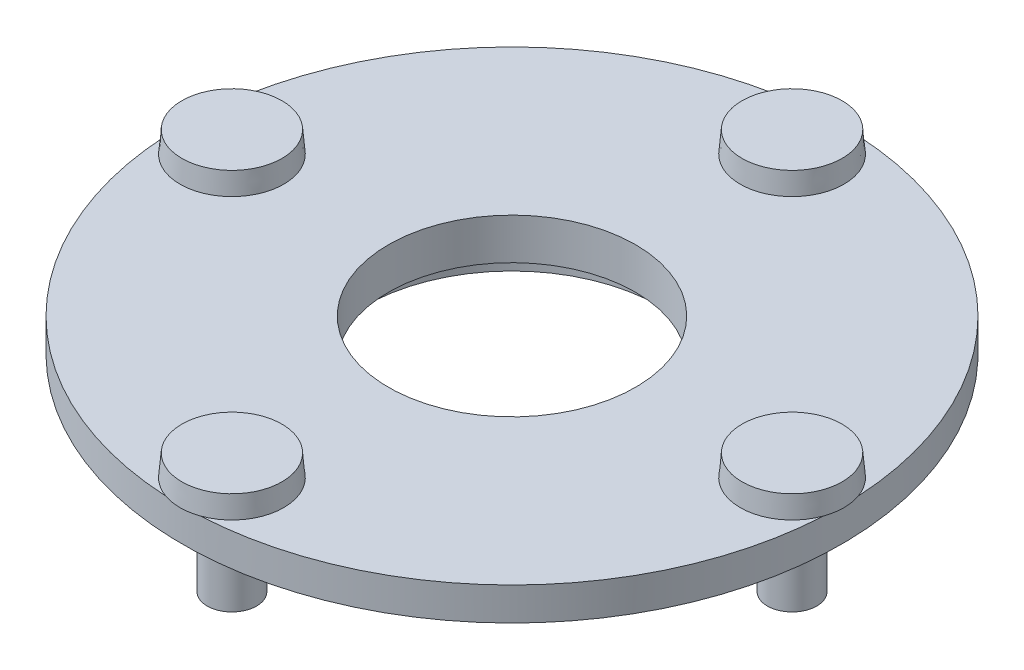
SolidWorks part; units mm, degrees
material "6061"
ref_plane "Front" through (0, 0, 0) normal (0, 0, 1) x (1, 0, 0)
ref_plane "Top" through (0, 0, 0) normal (0, 1, 0) x (1, 0, 0)
ref_plane "Right" through (0, 0, 0) normal (1, 0, 0) x (0, 0, -1)
sketch "Sketch1" plane through (0, 0, 0) normal (0, 0, 1) x (1, 0, 0)
  line L0 (0, -5.1764) -> (0, 49.1125) construction
  line L2 (7.5, 0) -> (20, 0)
  line L3 (7.5, 0) -> (7.5, 4)
  line L4 (7.5, 4) -> (20, 4)
  line L5 (20, 0) -> (20, 4)
  dimension "D1" = 40
  dimension "D2" = 15
  dimension "D3" = 4
revolve "Revolve1" add sketch "Sketch1" angle 360 about L0
sketch "Sketch2" plane through (0, 0, 0) normal (0, 0, 1) x (1, 0, 0)
  line L0 (0, -1.2334) -> (0, 5.5547) construction
  line L1 (-20, 0) -> (20, 0) construction
  line L2 (20, 0) -> (14, 0)
  line L3 (20, 0) -> (20, 2)
  line L4 (20, 2) -> (14, 2)
  line L5 (14, 0) -> (14, 2)
  line L6 (7.5, 0) -> (9, 0)
  line L7 (7.5, 0) -> (7.5, 1.5)
  line L8 (7.5, 1.5) -> (9, 1.5)
  line L9 (9, 0) -> (9, 1.5)
  line L10 (7.5, 0) -> (7.5, 4) construction
  dimension "D1" = 18
  dimension "D2" = 28
  dimension "D3" = 2
revolve "Cut-Revolve1" cut sketch "Sketch2" angle 360 about L0
sketch "Sketch3" plane through (0, 4, 0) normal (0, 1, 0) x (1, 0, 0)
  circle A0 centre (17, 0) radius 3.15
  dimension "D1" = 6.3
  dimension "D2" = 17
extrude "Boss-Extrude1" add sketch "Sketch3" along normal blind 1.3
sketch "Sketch4" plane through (0, 2, 0) normal (0, -1, 0) x (1, 0, 0)
  circle A0 centre (17, 0) radius 1.5
  dimension "D1" = 3
extrude "Boss-Extrude2" add sketch "Sketch4" along normal blind 4
pattern_circular "CirPattern1" count 4 over 360 about axis through (0, -5.1764, 0) along (0, -1, 0) of "Boss-Extrude1", "Boss-Extrude2"
chamfer "Chamfer1" distance 1.3 angle 5 4 edges at (-3.15, 5.3, 17) (-17, 5.3, -3.15) (3.15, 5.3, -17) (17, 5.3, 3.15) first distance on face at (-3.15, 5.3, 17) first distance on face at (-17, 5.3, -3.15) first distance on face at (3.15, 5.3, -17) first distance on face at (17, 5.3, 3.15)
